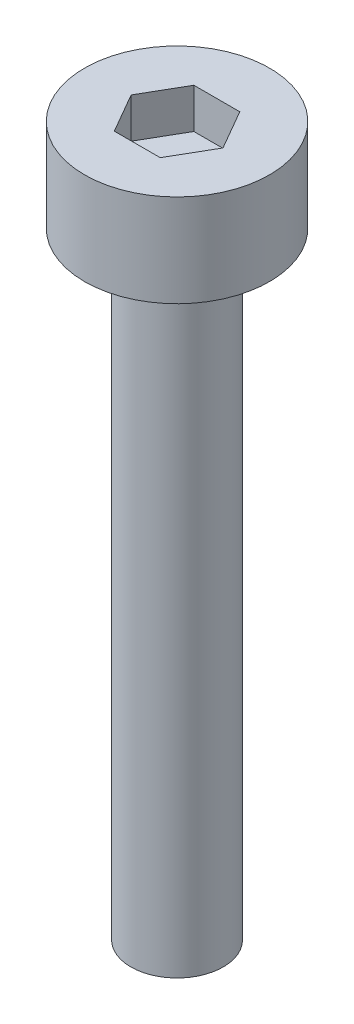
SolidWorks part; units mm, degrees
ref_plane "Front Plane" through (0, 0, 0) normal (0, 0, 1) x (1, 0, 0)
ref_plane "Top Plane" through (0, 0, 0) normal (0, 1, 0) x (1, 0, 0)
ref_plane "Right Plane" through (0, 0, 0) normal (1, 0, 0) x (0, 0, -1)
sketch "Sketch1" plane through (0, 0, 0) normal (0, 1, 0) x (1, 0, 0)
  circle A0 centre (0, 0) radius 1.5
  dimension "D1" = 3
extrude "ScrewShaft" add sketch "Sketch1" along normal blind 20
sketch "Sketch2" plane through (0, 20, 0) normal (0, 1, 0) x (1, 0, 0)
  circle A0 centre (0, 0) radius 3
  dimension "D1" = 6
extrude "Boss-Extrude2" add sketch "Sketch2" along normal blind 3
sketch "Sketch3" plane through (0, 23, 0) normal (0, 1, 0) x (1, 0, 0)
  line L0 (0, 0) -> (0, 1.29) construction
  line L1 (1.4896, 0) -> (0.7448, 1.29)
  line L2 (0.7448, 1.29) -> (-0.7448, 1.29)
  line L3 (-0.7448, 1.29) -> (-1.4896, 0)
  line L4 (-1.4896, 0) -> (-0.7448, -1.29)
  line L5 (-0.7448, -1.29) -> (0.7448, -1.29)
  line L6 (0.7448, -1.29) -> (1.4896, 0)
  circle A0 centre (0, 0) radius 1.29 construction
  dimension "D1" = 2.58
extrude "Cut-Extrude1" cut sketch "Sketch3" against normal blind 1.3
equation "\"X-ROD-SPACING\"=45"
equation "\"Y-ROD-SPACING\"=75"
equation "\"Z-ROD-SPACING\"=17.5"
equation "\"Y-BED-OFFSET\"=2"
equation "\"Y-BED-ROD-INSET\"=3.5"
equation "\"T-SLOT-NUT-FILLET-RADIUS\"=0.5"
equation "\"T-SLOT-SCREW-SHAFT-RADIUS\"=1.55"
equation "\"T-SLOT-SCREW-SHAFT-CUTOUT-LENGTH\"=11"
equation "\"T-SLOT-NUT-DEPTH\"=3.5"
equation "\"T-SLOT-NUT-WIDTH\"=2.85"
equation "\"T-SLOT-NUT-END-DISTANCE\"=8"
equation "\"ACRYLIC-THICKNESS\"=10"
equation "\"ACRYLIC-THICKNESS2\"=4.5"
equation "\"ACRYLIC-TAB-CUTOUT-SIZE\"=\"ACRYLIC-THICKNESS\"+\"ACRYLIC-TAB-TOLERANCE\"*2"
equation "\"ACRYLIC-TAB-WIDTH\"=\"ACRYLIC-THICKNESS\""
equation "\"ACRYLIC-M3-HOLE\"=2.9"
equation "\"SMOOTHROD-CAP-SCREW-DISTANCE\"=20"
equation "\"FRAME-WIDTH-INNER\"=370"
equation "\"NEMA17-HOLE-SPACING\"=31"
equation "\"NEMA17-CENTRAL-CUTOUT\"=22.5"
equation "\"Z-BRACKET-REACH\"=55"
equation "\"TOP-BRACKET-SPACING\"=40"
equation "\"SMOOTHROD-X-LENGTH\"=350"
equation "\"SMOOTHROD-Y-LENGTH\"=350"
equation "\"SMOOTHROD-Z-LENGTH\"=350"
equation "\"SMOOTHROD-TIGHTENING-HEADROOM\"=.25"
equation "\"LEADSCREW-Z-LENGTH\"=300"
equation "\"SCREW-LENGTH-FRAME\"=\"ACRYLIC-THICKNESS\" + 10"
equation "\"SCREW-HEAD-RADIUS\"=6"
equation "\"PRINTED-X-SMOOTHROD-DIAMETER\"=9.0"
equation "\"PRINTED-X-SMOOTHROD-CUTOUT\"=10"
equation "\"PRINTED-X-BASE-HEIGHT\"=10"
equation "\"PRINTED-LM8UU-CUTOUT-SIZE\"=15.5"
equation "\"PRINTED-LM8UU-CUTOUT-LENGTH\"=24.5"
equation "\"PRINTED-X-IDLER-HEIGHT\"=16"
equation "\"PSU-MOUNTING-WIDTH\"=95"
equation "\"PSU-MOUNTING-HEIGHT\"=177"
equation "\"D1@ScrewShaft\"=\"SCREW-LENGTH-FRAME\""
equation "\"D1@Sketch2\"=\"SCREW-HEAD-RADIUS\""
